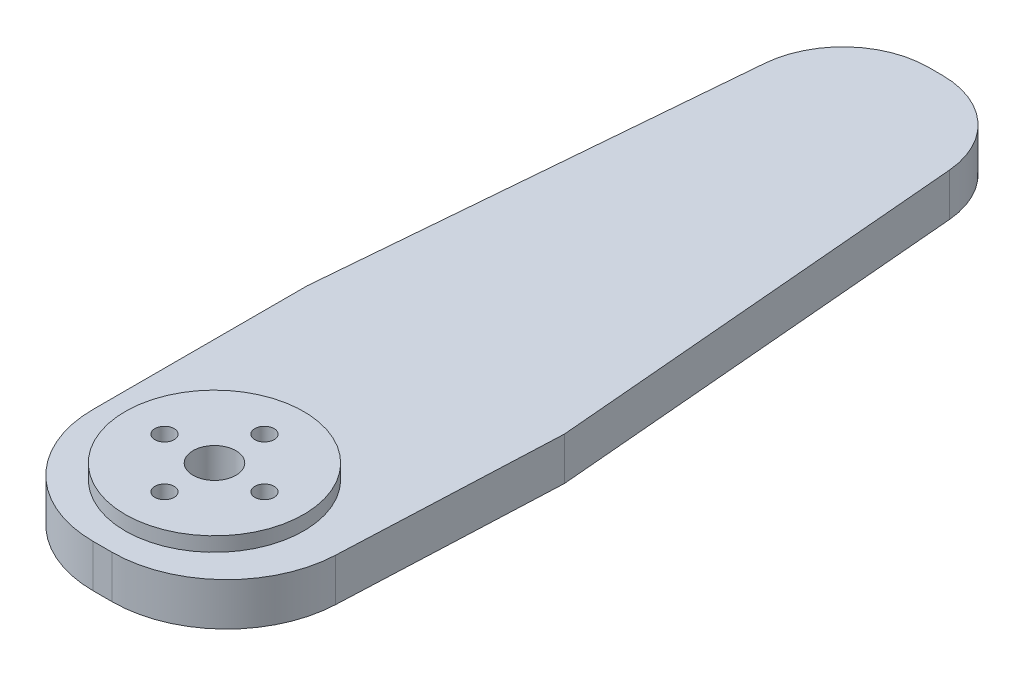
SolidWorks part; units mm, degrees
ref_plane "Front Plane" through (0, 0, 0) normal (0, 0, 1) x (1, 0, 0)
ref_plane "Top Plane" through (0, 0, 0) normal (0, 1, 0) x (1, 0, 0)
ref_plane "Right Plane" through (0, 0, 0) normal (1, 0, 0) x (0, 0, -1)
sketch "S_prism1" plane through (0, 0, 0) normal (0, 1, 0) x (1, 0, 0)
  line L0 (-1, -16) -> (1.6805, -16)
  line L1 (17.6654, -0.695) -> (19, 30)
  line L2 (19, 30) -> (13.9407, 89.0248)
  line L3 (1.9846, 100) -> (0.0154, 100)
  line L4 (-11.9407, 89.0248) -> (-17, 30)
  line L5 (-17, 30) -> (-17, 0)
  arc A0 (-17, 0) -> (-1, -16) centre (-1, 0) ccw
  arc A1 (1.6805, -16) -> (17.6654, -0.695) centre (1.6805, 0) ccw
  arc A2 (13.9407, 89.0248) -> (1.9846, 100) centre (1.9846, 88) ccw
  arc A3 (0.0154, 100) -> (-11.9407, 89.0248) centre (0.0154, 88) ccw
extrude "Boss_1" add sketch "S_prism1" along normal blind 6
ref_plane "PY_p6_000" through (0, 6, 0) normal (0, 1, 0) x (1, 0, 0)
sketch "S_cyl2" plane through (0, 6, 0) normal (0, 1, 0) x (1, 0, 0)
  circle A0 centre (0, 0) radius 12.5
  dimension "D1_S_cyl2" = 25
extrude "Boss_2" add sketch "S_cyl2" along normal blind 2
ref_plane "PY_m0_100" through (0, -0.1, 0) normal (0, 1, 0) x (1, 0, 0)
sketch "S_hole3" plane through (0, -0.1, 0) normal (0, 1, 0) x (1, 0, 0)
  circle A0 centre (0, 0) radius 3
  dimension "D1_S_hole3" = 6
extrude "Hole_3" cut sketch "S_hole3" along normal blind 8.2
sketch "S_hole4" plane through (0, -0.1, 0) normal (0, 1, 0) x (1, 0, 0)
  circle A0 centre (7, 0) radius 1.35
  dimension "D1_S_hole4" = 2.7
  dimension "P2" = 7
extrude "Hole_4" cut sketch "S_hole4" along normal blind 8.2
sketch "S_hole5" plane through (0, -0.1, 0) normal (0, 1, 0) x (1, 0, 0)
  circle A0 centre (0, -7) radius 1.35
  dimension "D1_S_hole5" = 2.7
  dimension "P2" = 7
extrude "Hole_5" cut sketch "S_hole5" along normal blind 8.2
sketch "S_hole6" plane through (0, -0.1, 0) normal (0, 1, 0) x (1, 0, 0)
  circle A0 centre (-7, 0) radius 1.35
  dimension "D1_S_hole6" = 2.7
  dimension "P2" = 7
extrude "Hole_6" cut sketch "S_hole6" along normal blind 8.2
sketch "S_hole7" plane through (0, -0.1, 0) normal (0, 1, 0) x (1, 0, 0)
  circle A0 centre (0, 7) radius 1.35
  dimension "D1_S_hole7" = 2.7
  dimension "P2" = 7
extrude "Hole_7" cut sketch "S_hole7" along normal blind 8.2
equation "\"plate_t\" = 3"
equation "\"clearance\" = 0.4"
